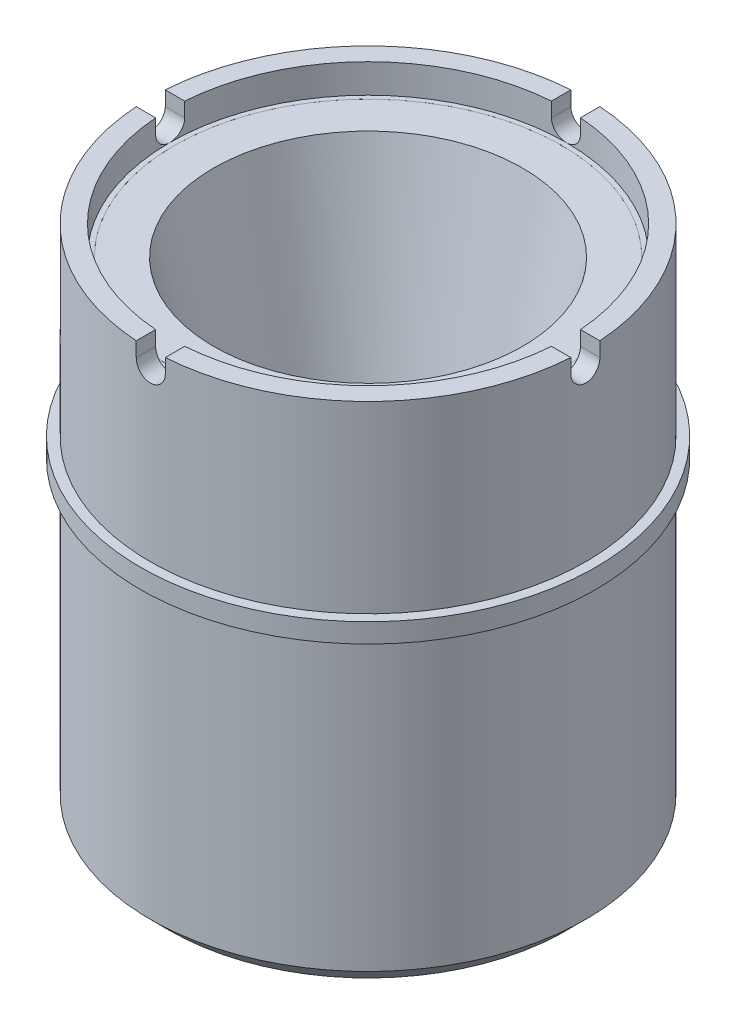
SolidWorks part; units mm, degrees
note: '?' marks a value the reader was unsure of.
other "球壳" parameters "D1"=81.3186, "D2"=14.2181, "D3"=3.8444, "D4"=46, "D5"=11.364, "D6"=4.1959, "D7"=3.7916, "D8"=4.4493, "D9"=3.4003, "D10"=2, "D11"=15.2084, "D12"=9.9715, "D13"=4.0911
ref_plane "前视基准面" through (0, 0, 0) normal (0, 0, 1) x (1, 0, 0)
ref_plane "上视基准面" through (0, 0, 0) normal (0, 1, 0) x (1, 0, 0)
ref_plane "右视基准面" through (0, 0, 0) normal (1, 0, 0) x (0, 0, -1)
other "Configuration Table"
sketch "草图1" plane through (0, 0, 0) normal (0, 0, 1) x (1, 0, 0)
  line L0 (0, 0) -> (0, 17.6209) construction
  line L1 (0, 0) -> (22.5, 0)
  line L2 (22.5, 0) -> (22.5, 50)
  line L3 (22.5, 50) -> (20, 50)
  line L4 (20, 50) -> (20, 48)
  line L5 (20, 48) -> (19, 48)
  line L6 (19, 48) -> (19, 4)
  line L7 (19, 4) -> (0, 4)
  line L8 (0, 4) -> (0, 0)
  line L10 (19, 4) -> (18, 4)
  line L11 (19, 4) -> (19, 6)
  line L12 (19, 6) -> (18, 6)
  line L13 (18, 4) -> (18, 6)
  line L14 (22.5, 32) -> (23.5, 32)
  line L15 (22.5, 32) -> (22.5, 34)
  line L16 (22.5, 34) -> (23.5, 34)
  line L17 (23.5, 32) -> (23.5, 34)
  line L18 (22.5, 50) -> (20.5, 50)
  line L19 (22.5, 50) -> (22.5, 53)
  line L20 (22.5, 53) -> (20.5, 53)
  line L21 (20.5, 50) -> (20.5, 53)
  dimension "D1" = 4
  dimension "D4" = 19
  dimension "D5" = 22.5
  dimension "D2" = 2
  dimension "D3" = 50
  dimension "D6" = 18
  dimension "D7" = 2
  dimension "D8" = 32
  dimension "D9" = 2
  dimension "D10" = 23.5
  dimension "D11" = 20
  dimension "D12" = 2
  dimension "D13" = 3
revolve "旋转" add sketch "草图1" angle 360 about L0
sketch "草图2" plane through (0, 0, 0) normal (0, 0, 1) x (1, 0, 0)
  line L0 (19, 48) -> (19, 4) construction
  line L1 (19, 6) -> (18, 6) construction
  line L2 (18, 4) -> (18, 6) construction
  line L3 (19, 4) -> (0, 4) construction
  line L4 (19, 48) -> (19, 4)
  line L5 (19, 6) -> (18, 6)
  line L6 (18, 4) -> (18, 6)
  line L7 (19, 4) -> (0, 4)
  line L9 (0, 0) -> (0, 64.7268) construction
  line L10 (0, 13) -> (0, 4)
  line L11 (20, 48) -> (19, 48) construction
  line L12 (20, 50) -> (20, 48) construction
  line L13 (20, 48) -> (19, 48)
  line L14 (20, 50) -> (20, 48)
  line L15 (20, 50) -> (0, 50)
  line L16 (0, 50) -> (0, 13)
  line L17 (19, 38) -> (0, 38)
  line L18 (12.5, 25.5) -> (19, 25.5)
  line L19 (19, 38) -> (12.5, 38)
  line L20 (19, 38) -> (19, 13)
  arc A0 (0, 13) -> (0, 38) centre (0, 25.5) ccw
  dimension "D2" = 12.5
  dimension "D1" = 12
revolve "下球座" add sketch "草图2" angle 360 about L9
sketch "草图3" plane through (0, 0, 0) normal (0, 0, 1) x (1, 0, 0)
  line L0 (0, 25.5) -> (6.5648, 50) construction
  line L1 (20, 50) -> (0, 50) construction
  line L2 (0, 50) -> (0, 13) construction
  line L3 (20, 48) -> (19, 48) construction
  line L4 (19, 48) -> (19, 4) construction
  line L5 (20, 50) -> (20, 48) construction
  line L6 (20, 48) -> (19, 48)
  line L7 (19, 48) -> (19, 4)
  line L8 (20, 50) -> (20, 48)
  line L9 (20, 50) -> (0, 50)
  line L10 (0, 50) -> (0, 13)
  line L11 (12.5, 25.5) -> (19, 25.5) construction
  line L12 (11.6004, 30.1563) -> (15.9643, 50)
  line L13 (12.5, 25.5) -> (19, 25.5)
  arc A0 (0, 13) -> (0, 38) centre (0, 25.5) ccw construction
  arc A1 (0, 13) -> (0, 38) centre (0, 25.5) ccw
  dimension "D1" = 15
  dimension "D2" = 10
  dimension "D3" = 2.597
revolve "上球座" add sketch "草图3" angle 360 about L10
sketch "草图4" plane through (0, 0, 0) normal (0, 0, 1) x (1, 0, 0)
  line L0 (0, 53) -> (0, 0) construction
  line L1 (22.5, 53) -> (-22.5, 53) construction
  line L3 (-1.5, 53) -> (1.5, 53)
  line L4 (-1.5, 53) -> (-1.5, 51.5)
  line L6 (1.5, 53) -> (1.5, 51.5)
  line L7 (15.9643, 50) -> (-15.9643, 50) construction
  line L8 (15.9643, 50) -> (-15.9643, 50)
  arc A0 (-1.5, 51.5) -> (1.5, 51.5) centre (0, 51.5) ccw
  dimension "D1" = 3
extrude "切除-拉伸1" cut sketch "草图4" against normal up to next contours L0 L3 L4 A0 | L3 L0 A0 L6
ref_axis "基准轴1" through (0, 32, 0) along (0, -1, 0)?
pattern_circular "阵列(圆周)1" count 4 over 360 about axis through (0, 0, 0) along (0, 1, 0) of "切除-拉伸1"
chamfer "倒角1" distance 2 angle 45 1 edges at (0, 0, -22.5)
equation "\"壳体外径\" = 45"
equation "\"壳体总高\" = 50"
equation "\"壳体内孔\" = 38"
equation "\"收口端内孔\" = 41"
equation "\"底部封闭端厚\" = 4"
equation "\"定位台阶内径\" = 36"
equation "\"定位台阶高\" = 2"
equation "\"压装段长\" = 32"
equation "\"收口翻边宽\" = 3"
equation "\"球头直径\" = 25"
equation "\"上球座法兰外径\" = 40"
equation "\"上球座法兰厚\" = 2"
equation "\"上球座高\" = 12"
equation "\"防尘罩下卡径\"= 44"
equation "\"防尘罩上卡径\"= 16"
equation "\"防尘罩自由高\"= 28"
equation "\"球销杆部直径\"= 15"
equation "\"收口端壁厚\" = (\"壳体外径\" - \"收口端内孔\") / 2"
equation "\"D1@草图1\"=\"底部封闭端厚\""
equation "\"D4@草图1\"=\"壳体内孔\"/2"
equation "\"D5@草图1\"=\"壳体外径\"/2"
equation "\"D2@草图1\"=\"上球座法兰厚\""
equation "\"D3@草图1\"=\"壳体总高\""
equation "\"D6@草图1\"=\"定位台阶内径\"/2"
equation "\"D7@草图1\"=\"定位台阶高\""
equation "\"D8@草图1\"=\"压装段长\""
equation "\"D9@草图1\"=\"压装段法兰厚\""
equation "\"压装段法兰厚\" = 2"
equation "\"压装段法兰外径\" = \"壳体外径\" + 2"
equation "\"D10@草图1\"=\"压装段法兰外径\"/2"
equation "\"D11@草图1\"=\"上球座法兰外径\"/2"
equation "\"D12@草图1\"=\"收口端壁厚\""
equation "\"D13@草图1\"=\"收口翻边宽\""
equation "\"D1@草图2\"=\"上球座高\""
equation "\"D2@草图2\"=\"球头直径\"/2"
equation "\"单平面球铰行程\" = 30"
equation "\"D1@草图3\"=\"单平面球铰行程\"/2"
equation "\"锥面大端直径\" = 20"
equation "\"锥度比\" = 11"
equation "\"锥度\" = atn(1 / \"锥度比\")"
equation "\"D2@草图3\"=\"锥面大端直径\"/2"
equation "\"D3@草图3\"=\"锥度\"/2"
